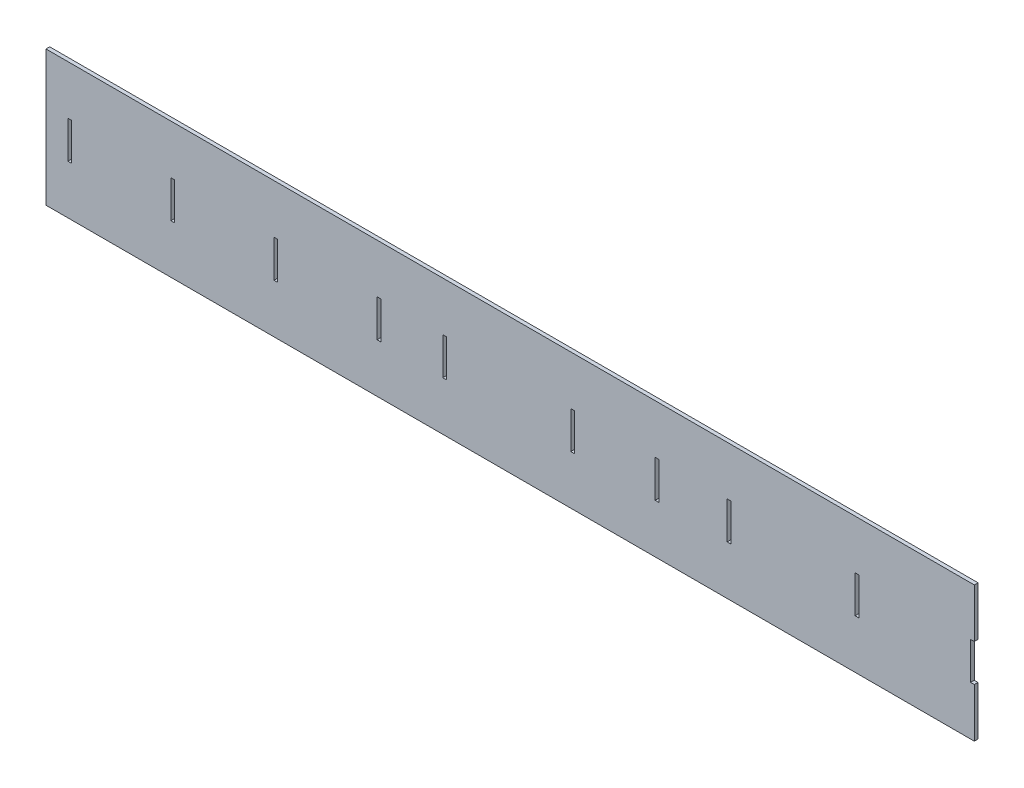
SolidWorks part; units mm, degrees
ref_plane "Front Plane" through (0, 0, 0) normal (0, 0, 1) x (1, 0, 0)
ref_plane "Top Plane" through (0, 0, 0) normal (0, 1, 0) x (1, 0, 0)
ref_plane "Right Plane" through (0, 0, 0) normal (1, 0, 0) x (0, 0, -1)
sketch "Sketch1" plane through (0, 0, 0) normal (0, 0, 1) x (1, 0, 0)
  line L1 (110.3511, 109) -> (858, 109)
  line L3 (858, 0) -> (110.3511, 0)
  line L4 (1244.614, 54.5) -> (110.3511, 54.5) construction
  line L5 (128, 69.5) -> (131, 69.5)
  line L6 (128, 69.5) -> (128, 39.5)
  line L7 (128, 39.5) -> (131, 39.5)
  line L8 (131, 69.5) -> (131, 39.5)
  line L14 (211, 69.5) -> (214, 69.5)
  line L15 (211, 69.5) -> (211, 39.5)
  line L16 (211, 39.5) -> (214, 39.5)
  line L17 (214, 69.5) -> (214, 39.5)
  line L18 (294, 69.5) -> (297, 69.5)
  line L19 (294, 69.5) -> (294, 39.5)
  line L20 (294, 39.5) -> (297, 39.5)
  line L21 (297, 69.5) -> (297, 39.5)
  line L22 (377, 69.5) -> (380, 69.5)
  line L23 (377, 69.5) -> (377, 39.5)
  line L24 (377, 39.5) -> (380, 39.5)
  line L25 (380, 69.5) -> (380, 39.5)
  line L26 (430, 69.5) -> (433, 69.5)
  line L27 (430, 69.5) -> (430, 39.5)
  line L28 (430, 39.5) -> (433, 39.5)
  line L29 (433, 69.5) -> (433, 39.5)
  line L30 (533, 69.5) -> (536, 69.5)
  line L31 (533, 69.5) -> (533, 39.5)
  line L32 (533, 39.5) -> (536, 39.5)
  line L33 (536, 69.5) -> (536, 39.5)
  line L34 (601, 69.5) -> (604, 69.5)
  line L35 (601, 69.5) -> (601, 39.5)
  line L36 (601, 39.5) -> (604, 39.5)
  line L37 (604, 69.5) -> (604, 39.5)
  line L38 (659, 69.5) -> (662, 69.5)
  line L39 (659, 69.5) -> (659, 39.5)
  line L40 (659, 39.5) -> (662, 39.5)
  line L41 (662, 69.5) -> (662, 39.5)
  line L42 (762, 69.5) -> (765, 69.5)
  line L43 (762, 69.5) -> (762, 39.5)
  line L44 (762, 39.5) -> (765, 39.5)
  line L45 (765, 69.5) -> (765, 39.5)
  line L46 (855, 69.5) -> (858, 69.5)
  line L47 (855, 69.5) -> (855, 39.5)
  line L48 (855, 39.5) -> (858, 39.5)
  line L53 (858, 69.5) -> (858, 109)
  line L54 (858, 39.5) -> (858, 0)
  line L55 (110.3511, 109) -> (110.3511, 0)
  dimension "D1" = 109
  dimension "D2" = 30
  dimension "D3" = 3
  dimension "D4" = 17.6489
  dimension "D8" = 30
  dimension "D9" = 3
  dimension "D10" = 30
  dimension "D11" = 3
  dimension "D12" = 80
  dimension "D13" = 80
  dimension "D14" = 80
  dimension "D15" = 3
  dimension "D16" = 30
  dimension "D17" = 50
  dimension "D18" = 3
  dimension "D19" = 30
  dimension "D20" = 100
  dimension "D21" = 3
  dimension "D22" = 30
  dimension "D23" = 65
  dimension "D24" = 30
  dimension "D25" = 3
  dimension "D26" = 55
  dimension "D27" = 3
  dimension "D28" = 30
  dimension "D29" = 3
  dimension "D30" = 30
  dimension "D31" = 100
  dimension "D32" = 90
  dimension "D33" = 3
  dimension "D34" = 30
extrude "Boss-Extrude1" add sketch "Sketch1" along normal blind 3
